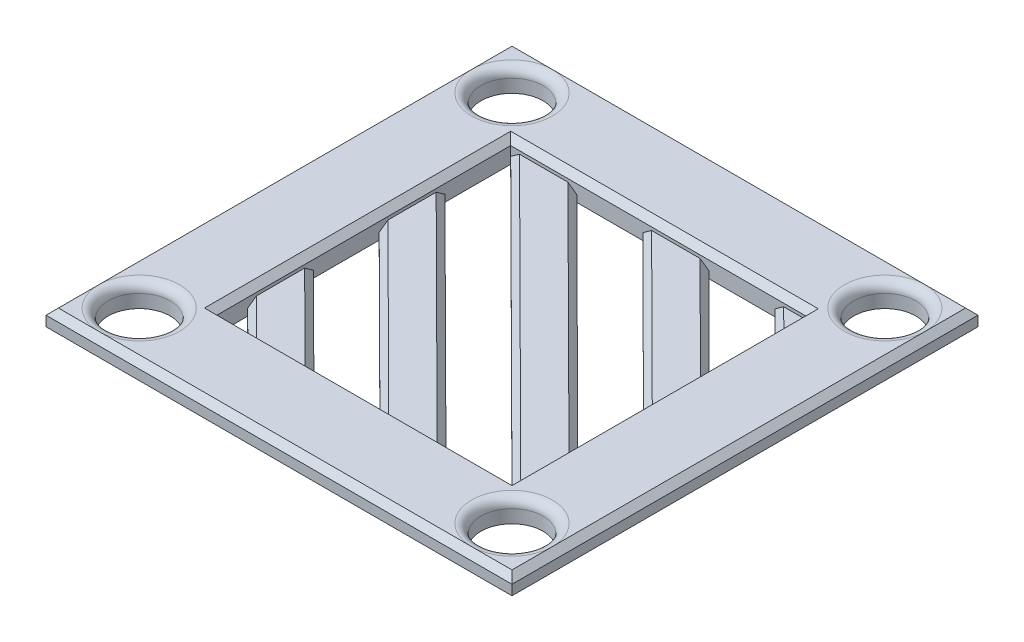
SolidWorks part; units mm, degrees
ref_plane "Front Plane" through (0, 0, 0) normal (0, 0, 1) x (1, 0, 0)
ref_plane "Top Plane" through (0, 0, 0) normal (0, 1, 0) x (1, 0, 0)
ref_plane "Right Plane" through (0, 0, 0) normal (1, 0, 0) x (0, 0, -1)
sketch "Sketch1" plane through (0, 0, 0) normal (0, 1, 0) x (1, 0, 0)
  line L0 (-381, 381) -> (-342.9, 381)
  line L1 (0, 0) -> (-381, 0)
  line L2 (0, 0) -> (0, 381)
  line L3 (0, 381) -> (-381, 381)
  line L4 (-381, 0) -> (-381, 381)
  line L5 (-284.2688, 337.0875) -> (-42.9688, 96.8502) construction
  line L6 (-381, 0) -> (-342.9, 0)
  line L7 (0, 381) -> (-38.1, 381)
  line L8 (0, 0) -> (-38.1, 0)
  line L9 (-95.1467, 310.0873) -> (-69.85, 284.9021)
  line L10 (-311.15, 190.5) -> (-311.15, 202.5613)
  line L11 (-311.15, 190.5) -> (-311.15, 148.7983)
  line L12 (-311.15, 69.85) -> (-285.8533, 69.85)
  line L13 (-69.85, 123.613) -> (-69.85, 177.376)
  line L14 (-95.1467, 310.0873) -> (-149.1475, 310.0873)
  line L15 (-311.15, 310.0873) -> (-69.85, 69.85)
  line L16 (-311.15, 256.3243) -> (-123.8508, 69.85)
  line L17 (-257.1492, 310.0873) -> (-69.85, 123.613)
  line L18 (-311.15, 202.5613) -> (-177.8517, 69.85)
  line L19 (-203.1483, 310.0873) -> (-69.85, 177.376)
  line L20 (-257.3875, 364.0877) -> (-16.0875, 123.8503) construction
  line L21 (-149.1475, 310.0873) -> (-69.85, 231.1391)
  line L22 (-231.8525, 69.85) -> (-177.8517, 69.85)
  line L23 (-311.15, 95.0352) -> (-311.15, 69.85)
  line L24 (-311.15, 95.0352) -> (-285.8533, 69.85)
  line L25 (-311.15, 256.3243) -> (-311.15, 310.0873)
  line L26 (-311.15, 148.7983) -> (-231.8525, 69.85)
  line L27 (-123.8508, 69.85) -> (-69.85, 69.85)
  line L28 (-364.9125, 256.087) -> (-123.6125, 15.8497) construction
  line L29 (-338.0312, 283.0872) -> (-96.7312, 42.8498) construction
  line L30 (-203.1483, 310.0873) -> (-257.1492, 310.0873)
  line L31 (-69.85, 231.1391) -> (-69.85, 284.9021)
  circle A0 centre (-342.9, 342.9) radius 25.4
  circle A1 centre (-342.9, 38.1) radius 25.4
  circle A2 centre (-38.1, 342.9) radius 25.4
  circle A3 centre (-38.1, 38.1) radius 25.4
  dimension "D5" = 38.1
  dimension "D4" = 50.8
  dimension "D7" = 50.8
  dimension "D10" = 50.8
  dimension "D1" = 381
  dimension "D2" = 381
  dimension "D3" = 38.1
  dimension "D6" = 38.1
  dimension "D8" = 38.1
  dimension "D9" = 38.1
  dimension "D13" = 38.1
  dimension "D14" = 120.65
  dimension "D15" = 38.1
  dimension "D16" = 38.1
extrude "Boss-Extrude2" add sketch "Sketch1" along normal blind 18.3564 contours L4 L1 L2 L3 L0 A3 A2 A1 A0 L31 L21 L14 L9 L30 L19 L13 L17 L27 L16 L25 L15 L26 L11 L10 L18 L22 L23 L24 L12 region at (-361.95, 0, -375.6118)
sketch "Sketch3" plane through (0, 18.3564, 0) normal (0, 1, 0) x (1, 0, 0)
  line L1 (-69.85, 177.376) -> (-69.85, 310.0873)
  line L2 (-311.15, 310.0873) -> (-69.85, 310.0873)
  line L3 (-311.15, 310.0873) -> (-311.15, 69.85)
  line L4 (-311.15, 69.85) -> (-69.85, 69.85)
  line L5 (-69.85, 69.85) -> (-69.85, 177.376)
extrude "Cut-Extrude1" cut sketch "Sketch3" against normal blind 7.62
fillet "Fillet1" radius 7.62 4 edges at (-342.9, 18.3564, -12.7) (-38.1, 18.3564, -12.7) (-38.1, 18.3564, -317.5) (-342.9, 18.3564, -317.5)
chamfer "Chamfer1" distance 5.08 angle 45 4 edges at (-190.5, 18.3564, -69.85) (-69.85, 18.3564, -189.9687) (-190.5, 18.3564, -310.0873) (-311.15, 18.3564, -189.9687)
chamfer "Chamfer2" distance 5.08 angle 45 9 edges at (-82.4983, 10.7364, -297.4947) (-109.4987, 10.7364, -270.6132) (-136.4992, 10.7364, -243.7317) (-163.4996, 10.7364, -216.8502) (-190.5, 10.7364, -189.9687) (-217.5004, 10.7364, -163.0872) (-244.5008, 10.7364, -136.2056) (-271.5013, 10.7364, -109.3241) (-298.5017, 10.7364, -82.4426)
chamfer "Chamfer3" distance 5.08 angle 45 4 edges at (-190.5, 18.3564, -381) (-381, 18.3564, -190.5) (-190.5, 18.3564, 0) (0, 18.3564, -190.5)
chamfer "Chamfer4" distance 5.08 angle 45 4 edges at (-381, 0, -190.5) (-190.5, 0, 0) (-190.5, 0, -381) (0, 0, -190.5)
chamfer "Chamfer8" distance 5.08 angle 45 2 edges at (-136.4992, 0, -243.7317) (-109.4987, 0, -270.6132)
